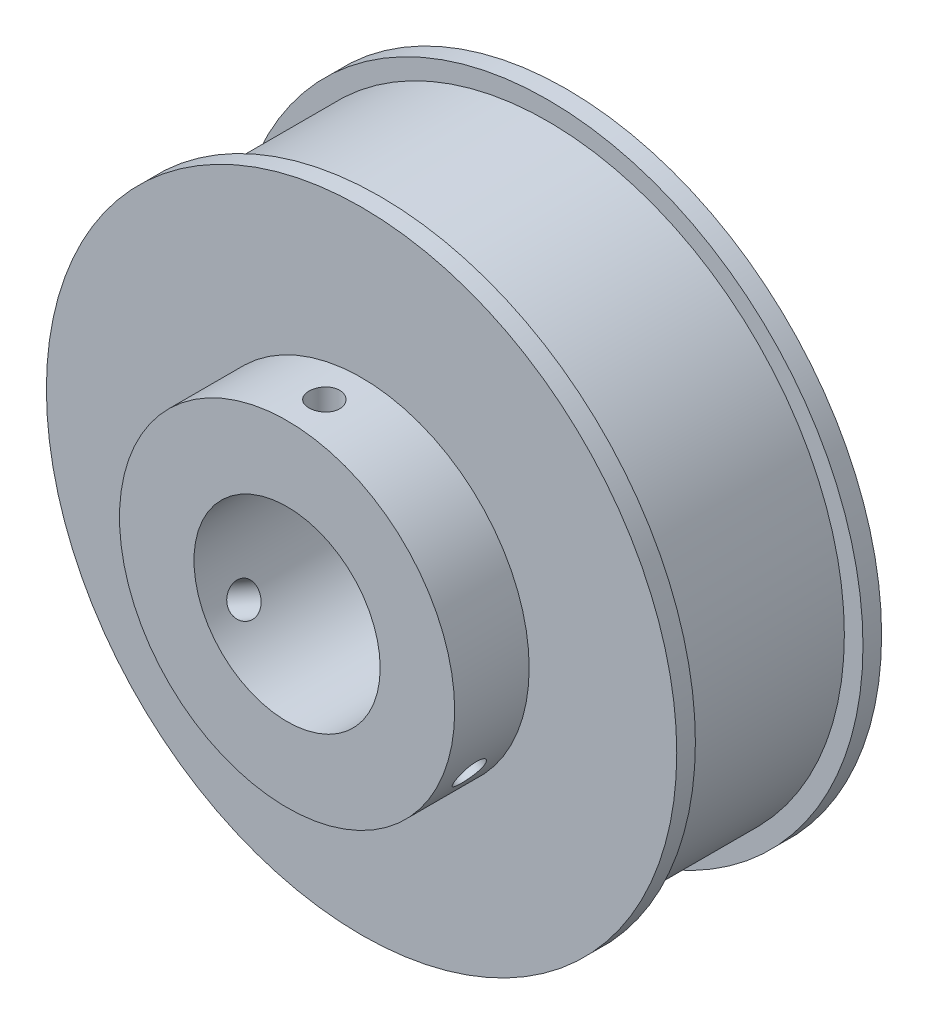
SolidWorks part; units mm, degrees
material "PA Type 6"
ref_plane "Front Plane" through (0, 0, 0) normal (0, 0, 1) x (1, 0, 0)
ref_plane "Top Plane" through (0, 0, 0) normal (0, 1, 0) x (1, 0, 0)
ref_plane "Right Plane" through (0, 0, 0) normal (1, 0, 0) x (0, 0, -1)
sketch "Sketch1" plane through (0, 0, 0) normal (0, 0, 1) x (1, 0, 0)
  circle A0 centre (0, 0) radius 31.85
  dimension "D1" = 63.7
extrude "Boss-Extrude1" add sketch "Sketch1" along normal blind 18
sketch "Sketch2" plane through (0, 0, 18) normal (0, 0, 1) x (1, 0, 0)
  circle A3 centre (0, 0) radius 33.85
  circle A4 centre (0, 0) radius 33.85
  dimension "D1" = 2
extrude "Boss-Extrude2" add sketch "Sketch2" along normal blind 2
extrude "Boss-Extrude3" add sketch "Sketch2<2>" against normal blind 2 from surface starting at face at (31.85, 0, 0)
sketch "Sketch2<2>" plane through (0, 0, 18) normal (0, 0, 1) x (1, 0, 0) same geometry as "Sketch2"
sketch "Sketch3" plane through (0, 0, 20) normal (0, 0, 1) x (1, 0, 0)
  point P0 (0, 0)
hole_wizard "Ø20.0mm Dowel Hole1" positions "Sketch3" profile "Sketch5" hole size "Ø20.0" standard "DIN" end condition through all
sketch "Sketch5" plane through (0, 0, 20) normal (1, 0, 0) x (0, -1, 0)
  line L0 (0, 0) -> (0, 22)
  line L1 (0, 22) -> (10, 22)
  line L2 (10, 22) -> (10, 0)
  line L5 (10, 0) -> (0, 0)
  line L11 (0, -6.35) -> (0, 107.95) construction
  dimension "Thru Hole Dia." = 20
  dimension "Thru Hole Depth" = 22
sketch "Sketch13" plane through (0, 0, 20) normal (0, 0, 1) x (1, 0, 0)
  circle A0 centre (0, 0) radius 10
  circle A1 centre (0, 0) radius 18
  dimension "D1" = 36
extrude "Boss-Extrude4" add sketch "Sketch13" along normal blind 8
sketch "Sketch15" plane through (0, 0, 0) normal (0, 1, 0) x (1, 0, 0)
  line L0 (-18, -20) -> (18, -20) construction
  point P0 (0, -24)
  dimension "D1" = 4
hole_wizard "Tap Drill for M4 Tap1" positions "Sketch15" profile "Sketch16" hole size "M4" standard "DIN" end condition through all
sketch "Sketch16" plane through (0, 0, 24) normal (1, 0, 0) x (0, 0, -1)
  line L0 (0, 0) -> (0, 33.85)
  line L1 (0, 33.85) -> (1.65, 33.85)
  line L2 (1.65, 33.85) -> (1.65, 0)
  line L5 (1.65, 0) -> (0, 0)
  line L11 (0, -6.35) -> (0, 107.95) construction
  dimension "Thru Hole Dia." = 3.3
  dimension "Thru Hole Depth" = 33.85
ref_axis "Axis1" through (0, 0, -2) along (0, 0, 1)
ref_plane "Plane4" through (-15.5885, -9, 0) normal (-0.866, -0.5, 0) x (0, 0, -1)
sketch "Sketch20" plane through (-15.5885, -9, 0) normal (-0.866, -0.5, 0) x (0, 0, -1)
  line L0 (2, 0) -> (-28, 0) construction
  line L1 (-20, 18) -> (-20, -18) construction
  point P0 (-24, 0)
  dimension "D1" = 4
hole_wizard "Tap Drill for M4 Tap3" positions "Sketch20" profile "Sketch21" hole size "M4" standard "DIN"
sketch "Sketch21" plane through (-15.5885, -9, 24) normal (0, 0, 1) x (0.5, -0.866, 0)
  line L0 (0, 0) -> (0, 17.8214)
  line L1 (0, 17.8214) -> (1.65, 16.83)
  line L2 (1.65, 16.83) -> (1.65, 0)
  line L5 (1.65, 0) -> (0, 0)
  line L10 (0, 17.8214) -> (-1.65, 16.83) construction
  line L11 (0, -6.35) -> (0, 107.95) construction
  dimension "Hole Dia." = 3.3
  dimension "Hole Depth" = 16.83
  dimension "Drill Angle" = 118
ref_plane "Plane5" through (15.5885, -9, 0) normal (0.866, -0.5, 0) x (0, 0, -1)
sketch "Sketch22" plane through (15.5885, -9, 0) normal (0.866, -0.5, 0) x (0, 0, -1)
  line L0 (2, 0) -> (-28, 0) construction
  line L1 (-20, 33.85) -> (-20, -33.85) construction
  point P0 (-24, 0)
  dimension "D1" = 4
hole_wizard "Tap Drill for M4 Tap4" positions "Sketch22" profile "Sketch23" hole size "M4" standard "DIN"
sketch "Sketch23" plane through (15.5885, -9, 24) normal (0, 0, 1) x (0.5, 0.866, 0)
  line L0 (0, 0) -> (0, 17.8214)
  line L1 (0, 17.8214) -> (1.65, 16.83)
  line L2 (1.65, 16.83) -> (1.65, 0)
  line L5 (1.65, 0) -> (0, 0)
  line L10 (0, 17.8214) -> (-1.65, 16.83) construction
  line L11 (0, -6.35) -> (0, 107.95) construction
  dimension "Hole Dia." = 3.3
  dimension "Hole Depth" = 16.83
  dimension "Drill Angle" = 118
